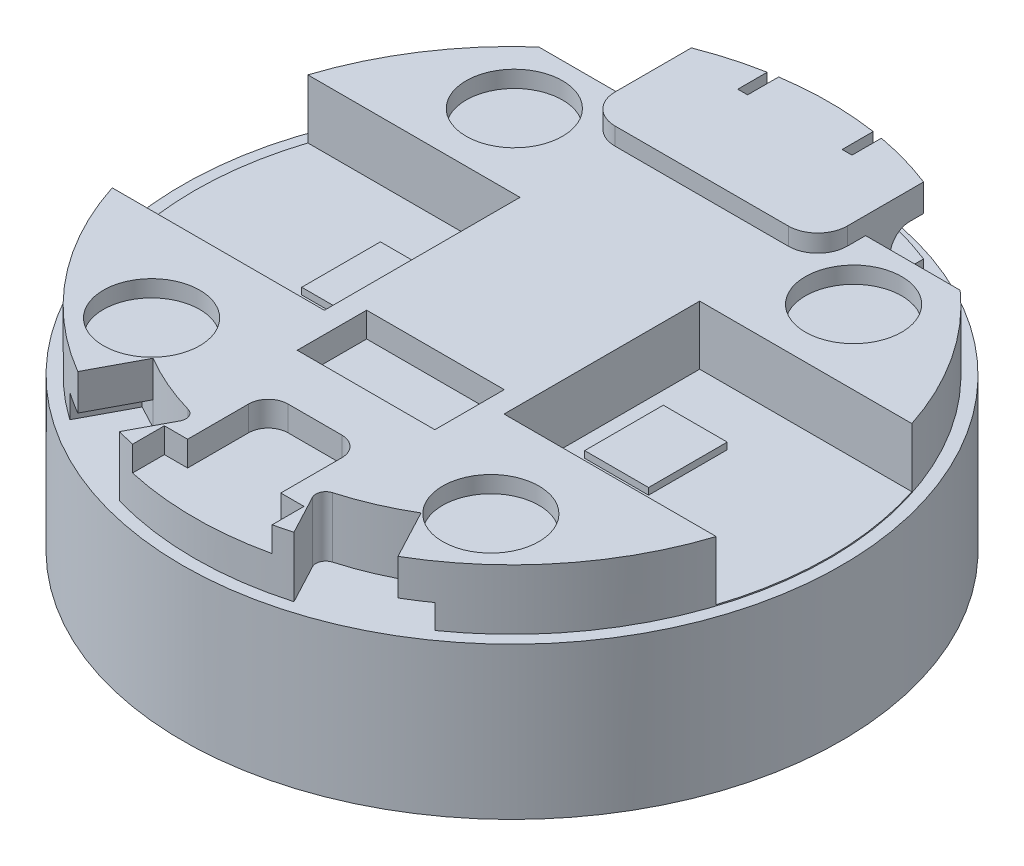
SolidWorks part; units mm, degrees
note: The reader was unsure of these and kept them because the rebuilt part matched: shared geometry of "Sketch26<4>", "Sketch26<7>".
ref_plane "Front Plane" through (0, 0, 0) normal (0, 0, 1) x (1, 0, 0)
ref_plane "Top Plane" through (0, 0, 0) normal (0, 1, 0) x (1, 0, 0)
ref_plane "Right Plane" through (0, 0, 0) normal (1, 0, 0) x (0, 0, -1)
sketch "Sketch1" plane through (0, 0, 0) normal (0, 1, 0) x (1, 0, 0)
  circle A0 centre (0, 0) radius 33.52
  dimension "D1" = 67.04
extrude "Boss-Extrude1" add sketch "Sketch1" along normal blind 9
sketch "Sketch2" plane through (0, 9, 0) normal (0, 1, 0) x (1, 0, 0)
  circle A0 centre (0, 0) radius 32.29
  dimension "D1" = 64.58
extrude "Boss-Extrude2" add sketch "Sketch2" along normal blind 6.12
sketch "Sketch3" plane through (0, 15.12, 0) normal (0, 1, 0) x (1, 0, 0)
  line L0 (0, 0) -> (0, 50000) construction
  line L1 (0, 0) -> (-50000, 0) construction
  line L2 (-11.81, 30.0528) -> (-11.81, 24.1537)
  line L3 (-11.81, 24.1537) -> (-21.43, 24.1537)
  line L4 (-11.81, 24.1537) -> (11.81, 24.1537) construction
  line L5 (11.81, 24.1537) -> (21.43, 24.1537)
  line L6 (11.81, 30.0528) -> (11.81, 24.1537)
  circle A0 centre (0, 0) radius 32.29 construction
  point P14 (0, 24.1537)
  circle M5 centre (0, 0) radius 32.29
  dimension "D1" = 9.62
  dimension "D2" = 11.81
extrude "Cut-Extrude1" cut sketch "Sketch3" against normal blind 6 contours L3 L2 M5 | L6 L5 M5
sketch "Sketch9" plane through (0, 15.12, 0) normal (0, 1, 0) x (1, 0, 0)
  line L0 (-11.81, 24.1537) -> (11.81, 24.1537) construction
  line L1 (-11.81, 28.6537) -> (11.81, 28.6537) construction
  line L2 (-11.81, 30.0528) -> (-11.81, 24.1537) construction
  line L3 (-11.81, 24.6537) -> (11.81, 24.6537) construction
  line L4 (11.81, 30.0528) -> (11.81, 24.1537) construction
  line L5 (0, 32.29) -> (-37.4588, 32.29) construction
  arc A1 (11.81, 30.0528) -> (-11.81, 30.0528) centre (0, 0) ccw construction
sketch "Sketch10" plane through (-11.81, 0, 0) normal (-1, 0, 0) x (0, 0, 1)
  line L0 (-28.6537, 15.12) -> (-28.6537, 9.12) construction
  line L1 (-30.0528, 9.12) -> (-24.1537, 9.12) construction
  line L2 (-24.6537, 15.12) -> (-24.6537, 9.12)
  line L3 (-33.7795, 12.12) -> (-23.5278, 12.12) construction
  line L4 (-28.6537, 9.12) -> (-35.6991, 9.12) construction
  line L5 (-28.6537, 10.12) -> (-37.7738, 10.12) construction
  circle A0 centre (-28.6537, 12.12) radius 2
  point P11 (-28.6537, 12.12)
  dimension "D1" = 4
extrude "Cut-Extrude2" cut sketch "Sketch10" against normal through all contours A0
ref_plane "Plane3" through (0, 0, 0) normal (-1, 0, 0) x (0, 0, 1)
sketch "Sketch19" plane through (0, 0, 0) normal (-1, 0, 0) x (0, 0, 1)
  line L0 (4.593, 17.1307) -> (4.593, -49982.8693) construction
  point P2 (-30.0416, 10.7027)
sketch "Sketch20" plane through (0, 0, 0) normal (-1, 0, 0) x (0, 0, 1)
  line L0 (-28.6537, 12.12) -> (-42.8447, 12.12) construction
sketch "Sketch23" plane through (-11.81, 0, 0) normal (-1, 0, 0) x (0, 0, 1)
  line L0 (-28.6537, 14.12) -> (-34.7082, 14.12)
  line L4 (-34.7082, 10.12) -> (-28.6537, 10.12)
  line L5 (-28.6537, 14.12) -> (-28.6537, 10.12)
  line L6 (-34.7082, 14.12) -> (-34.7082, 10.12)
  arc A0 (-30.0528, 10.6908) -> (-30.0528, 13.5492) centre (-28.6537, 12.12) ccw construction
extrude "Cut-Extrude3" cut sketch "Sketch23" against normal through all
sketch "Sketch24" plane through (0, 15.12, 0) normal (0, 1, 0) x (1, 0, 0)
  line L0 (0, 0) -> (-50000, 0) construction
  line L1 (0, 0) -> (0, 50000) construction
  line L2 (31.6, 6.6395) -> (19.5839, 6.6395)
  line L3 (19.5839, 6.6395) -> (19.5839, 0)
  line L4 (-2.2007, -32.2149) -> (-2.2007, -19.9749)
  line L5 (-2.2007, -19.9749) -> (0, -19.9749)
  line L6 (-11.81, 30.0528) -> (-11.81, 22.29)
  line L7 (-8.81, 19.29) -> (8.81, 19.29)
  line L8 (0, 32.29) -> (0, 19.29) construction
  line L9 (0, 32.29) -> (0, 19.29)
  line L10 (11.81, 30.0528) -> (11.81, 22.29)
  arc A0 (-21.43, 24.1537) -> (21.43, 24.1537) centre (0, 0) ccw construction
  arc A1 (11.81, 30.0528) -> (-11.81, 30.0528) centre (0, 0) ccw construction
  arc A2 (11.81, 22.29) -> (8.81, 19.29) centre (8.81, 22.29) cw
  arc A3 (-8.81, 19.29) -> (-11.81, 22.29) centre (-8.81, 22.29) cw
  point P26 (11.81, 19.29)
  point P29 (-11.81, 19.29)
  line M7 (-11.81, 30.0528) -> (-11.81, 24.1537)
  line M11 (11.81, 24.1537) -> (11.81, 30.0528)
  arc M12 (11.81, 30.0528) -> (-11.81, 30.0528) centre (0, 0) ccw
  dimension "D3" = 3
  dimension "D1" = 12.24
  dimension "D2" = 13
extrude "Boss-Extrude4" add sketch "Sketch24" along normal blind 1.78 contours A3 L7 L9 L6 M12 M7 | A2 L10 L9 L7 M11 M12
sketch "Sketch26" plane through (0, 15.12, 0) normal (0, 1, 0) x (1, 0, 0)
  line L0 (0, 0) -> (0, -50000) construction
  line L1 (0, 0) -> (-50000, 0) construction
  line L2 (30.7187, 9.95) -> (9.1387, 9.95)
  line L3 (9.1387, 9.95) -> (9.1387, -9.95)
  line L4 (30.7187, -9.95) -> (9.1387, -9.95)
  line L5 (-4.6587, 12.95) -> (4.6587, 12.95) construction
  line L6 (4.6587, 12.95) -> (4.6587, 0) construction
  line L7 (4.6587, 0) -> (4.6587, -14.85) construction
  line L8 (4.6587, -14.85) -> (0, -14.85) construction
  line L9 (-4.6587, -14.85) -> (0, -14.85) construction
  line L12 (0, 19.1985) -> (20.1, 19.1985) construction
  line L13 (20.1, 19.1985) -> (20.1, 9.95) construction
  line L14 (0, 32.1985) -> (-36.5688, 32.1985) construction
  line L15 (-7.1, -31.4997) -> (-7.1, -28.2597)
  line L16 (-7.1, -28.2597) -> (-4.74, -28.2597)
  line L17 (7.1, -31.4997) -> (7.1, -28.2597)
  line L19 (-4.74, -28.2597) -> (-4.74, -22.05)
  line L20 (-2.74, -20.05) -> (2.74, -20.05)
  line L21 (4.74, -28.2597) -> (4.74, -22.05)
  line L22 (0, -32.29) -> (21.7123, -32.29) construction
  line L23 (4.74, -28.2597) -> (7.1, -28.2597)
  line L26 (12.5921, 19.1985) -> (12.5921, 19.0001)
  line L27 (14.1577, 16.0217) -> (21.8513, 16.0217)
  line L40 (7, -14.85) -> (-7, -14.85)
  line L45 (-7, -14.85) -> (-7, -10.2285)
  line L46 (-7, -10.2285) -> (7, -10.2285)
  line L47 (7, -14.85) -> (7, -10.2285)
  line L48 (12.6302, 17.4892) -> (21.8766, 17.4892) construction
  line L50 (7.4988, -24.9826) -> (7.4988, -24.919)
  line L52 (8.0715, -24.9826) -> (8.0715, -24.919)
  line L53 (14.1577, 36.6941) -> (14.1577, 5.8809) construction
  arc A0 (-21.43, 24.1537) -> (21.43, 24.1537) centre (0, 0) ccw construction
  arc A2 (4.74, -22.05) -> (2.74, -20.05) centre (2.74, -22.05) ccw
  arc A3 (-2.74, -20.05) -> (-4.74, -22.05) centre (-2.74, -22.05) ccw
  circle A5 centre (17.2534, 17.4892) radius 4.9
  arc A6 (-14.4609, -22.3616) -> (-4.74, -26.2048) centre (0, 0) ccw
  circle A7 centre (17.2534, -19.4108) radius 4.9
  circle A8 centre (-17.2534, -19.4108) radius 4.9
  arc A9 (4.74, -26.2048) -> (15.2393, -21.8385) centre (0, 0) ccw
  circle A10 centre (-17.2534, 17.4892) radius 4.9
  point P10 (2.3294, -14.85)
  point P13 (9.1387, 0)
  point P22 (0, 12.95)
  point P31 (0, -28.2597)
  point P37 (0, -20.05)
  point P41 (4.74, -20.05)
  point P44 (-4.74, -20.05)
  point P63 (0, 0)
  point P66 (0, -10.2285)
  point P79 (14.1577, 21.2875)
  arc M17 (-21.43, 24.1537) -> (21.43, 24.1537) centre (0, 0) ccw
  dimension "D8" = 14.2
  dimension "D11" = 2
  dimension "D12" = 9.8
  dimension "D1" = 21.58
  dimension "D2" = 9.95
  dimension "D3" = 4.48
  dimension "D4" = 3
  dimension "D5" = 4.9
  dimension "D6" = 13
  dimension "D7" = 20.1
  dimension "D9" = 9.48
  dimension "D10" = 12.24
  dimension "D13" = 2
  dimension "D14" = 7
sketch "Sketch27" plane through (-11.81, 0, 0) normal (-1, 0, 0) x (0, 0, 1)
  line L0 (-28.4924, 16.9) -> (-35.5308, 16.9) construction
  line L1 (-30.0528, 16.9) -> (-22.29, 16.9) construction
extrude "Cut-Extrude5" cut sketch "Sketch26<4>" against normal blind 6 contours L4 L2 L3 M17
sketch "Sketch26<4>" plane through (0, 15.12, 0) normal (0, 1, 0) x (1, 0, 0) same geometry as "Sketch26"
extrude "Cut-Extrude6" cut sketch "Sketch26" against normal blind 2.54 contours L20 A3 L19 L16 L15 L17 L23 L21 A2 M17 | L40 L47 L46 L45
sketch "Sketch28" plane through (0, 15.12, 0) normal (0, 1, 0) x (1, 0, 0)
  line L0 (0, 0) -> (0, -50000) construction
  line L1 (-13.6253, -22.8803) -> (-16.283, -27.8839)
  line L2 (-6.1386, -25.9128) -> (-8.8666, -31.0488)
  line L3 (6.1386, -25.9128) -> (8.8666, -31.0488)
  line L4 (13.6253, -22.8803) -> (16.283, -27.8839)
  arc A0 (-13.6253, -22.8803) -> (-6.1386, -25.9128) centre (0, 0) ccw
  arc A1 (-21.43, 24.1537) -> (-7.1, -31.4997) centre (0, 0) ccw construction
  arc A2 (13.6253, -22.8803) -> (6.1386, -25.9128) centre (0, 0) cw
  arc M5 (7.1, -31.4997) -> (30.7187, -9.95) centre (0, 0) ccw
  arc M17 (-21.43, 24.1537) -> (-7.1, -31.4997) centre (0, 0) ccw
  dimension "D1" = 5.66
extrude "Cut-Extrude7" cut sketch "Sketch28" against normal up to surface (6.12 mm away) contours A0 L1 L2 M17 | L4 A2 L3 M5 up to face at (0, 9, 32.29)
sketch "Sketch30" plane through (-1.1486, 0, -0.6101) normal (0.8832, 0, 0.4691) x (0.4691, 0, -0.8832)
  line L0 (-32.2638, 12.66) -> (-26.5982, 12.66) construction
  line L1 (-32.2638, 11.46) -> (-26.5982, 11.46) construction
  line L3 (-32.2638, 12.66) -> (-26.5982, 12.66)
  line L4 (-32.2638, 9) -> (-26.5982, 9)
  line L5 (-26.5982, 9) -> (-26.5982, 15.12)
  line L6 (-26.5982, 15.12) -> (-32.2638, 15.12)
  line L7 (-32.2638, 15.12) -> (-32.2638, 9)
  line L8 (-32.2638, 9) -> (-26.5982, 9)
  line L9 (-26.5982, 9) -> (-26.5982, 15.12)
  line L10 (-26.5982, 15.12) -> (-32.2638, 15.12)
  line L11 (-32.2638, 15.12) -> (-32.2638, 9)
  line L12 (-32.2638, 12.66) -> (-32.2638, 11.46)
  line L13 (-32.2638, 11.46) -> (-26.5982, 11.46)
  line L14 (-26.5982, 12.66) -> (-26.5982, 11.46)
  line M7 (-32.2638, 9) -> (-26.5982, 9)
  line M8 (-26.5982, 9) -> (-26.5982, 15.12)
  dimension "D2" = 3.66
  dimension "D1" = 0
extrude "Cut-Extrude8" cut sketch "Sketch26<7>" against normal blind 1.7
sketch "Sketch26<7>" plane through (0, 15.12, 0) normal (0, 1, 0) x (1, 0, 0) same geometry as "Sketch26"
sketch "Sketch31" plane through (0, 16.9, 0) normal (0, 1, 0) x (1, 0, 0)
  line L0 (-5.81, 31.763) -> (-5.81, 28.77)
  line L1 (-4.81, 31.9297) -> (-4.81, 28.77)
  line L2 (-4.81, 28.77) -> (-5.81, 28.77)
  line L3 (-8.81, 19.29) -> (8.81, 19.29)
  line L4 (11.81, 22.29) -> (11.81, 30.0528)
  line L5 (-11.81, 30.0528) -> (-11.81, 22.29)
  line L6 (-8.81, 19.29) -> (8.81, 19.29)
  line L7 (11.81, 22.29) -> (11.81, 30.0528)
  line L8 (-11.81, 30.0528) -> (-11.81, 22.29)
  line L9 (0, 32.29) -> (-14.5468, 32.29) construction
  line L10 (0, 19.29) -> (0, 26.1672) construction
  line L11 (0, 4.2695) -> (0, -4.2695) construction
  line L12 (4.81, 28.77) -> (5.81, 28.77)
  line L13 (5.81, 31.763) -> (5.81, 28.77)
  line L14 (4.81, 31.9297) -> (4.81, 28.77)
  arc A3 (-11.81, 22.29) -> (-8.81, 19.29) centre (-8.81, 22.29) ccw
  arc A4 (8.81, 19.29) -> (11.81, 22.29) centre (8.81, 22.29) ccw
  arc A5 (11.81, 30.0528) -> (-11.81, 30.0528) centre (0, 0) ccw
  arc A6 (-11.81, 22.29) -> (-8.81, 19.29) centre (-8.81, 22.29) ccw
  arc A7 (8.81, 19.29) -> (11.81, 22.29) centre (8.81, 22.29) ccw
  arc A8 (11.81, 30.0528) -> (-11.81, 30.0528) centre (0, 0) ccw
  arc M16 (11.81, 30.0528) -> (-11.81, 30.0528) centre (0, 0) ccw
  dimension "D2" = 6
  dimension "D3" = 1
  dimension "D4" = 3.52
  dimension "D1" = 0
sketch "Sketch32" plane through (-1.1486, 0, -0.6101) normal (0.8832, 0, 0.4691) x (0.4691, 0, -0.8832)
sketch "Sketch33" plane through (-1.1486, 0, -0.6101) normal (0.8832, 0, 0.4691) x (0.4691, 0, -0.8832)
  line L0 (-32.2638, 11.46) -> (-26.5982, 11.46)
  line L2 (-32.2638, 12.66) -> (-32.2638, 11.46)
  line L4 (-26.5982, 12.66) -> (-26.5982, 11.46)
  line L8 (-32.2638, 9) -> (-26.5982, 9)
  line L9 (-26.5982, 9) -> (-26.5982, 15.12)
  line L10 (-26.5982, 15.12) -> (-32.2638, 15.12)
  line L11 (-32.2638, 15.12) -> (-32.2638, 9)
  line L12 (-32.2638, 9) -> (-26.5982, 9)
  line L13 (-26.5982, 9) -> (-26.5982, 15.12)
  line L14 (-26.5982, 15.12) -> (-32.2638, 15.12)
  line L15 (-32.2638, 15.12) -> (-32.2638, 9)
  dimension "D1" = 0
sketch "Sketch36" plane through (-1.1486, 0, -0.6101) normal (0.8832, 0, 0.4691) x (0.4691, 0, -0.8832)
  line L0 (-32.2638, 11.56) -> (-26.5982, 11.56)
  line L4 (-32.2638, 9) -> (-26.5982, 9)
  line L5 (-26.5982, 9) -> (-26.5982, 15.12)
  line L6 (-26.5982, 15.12) -> (-32.2638, 15.12)
  line L7 (-32.2638, 15.12) -> (-32.2638, 9)
  line L8 (-32.2638, 9) -> (-26.5982, 9)
  line L9 (-26.5982, 9) -> (-26.5982, 15.12)
  line L10 (-26.5982, 15.12) -> (-32.2638, 15.12)
  line L11 (-32.2638, 15.12) -> (-32.2638, 9)
  dimension "D2" = 2.56
  dimension "D1" = 0
sketch "Sketch37" plane through (1.1486, 0, -0.6101) normal (-0.8832, 0, 0.4691) x (0.4691, 0, 0.8832)
  line L0 (32.2638, 11.46) -> (26.5982, 11.46)
  line L4 (32.2638, 9) -> (32.2638, 15.12)
  line L5 (32.2638, 15.12) -> (26.5982, 15.12)
  line L6 (26.5982, 15.12) -> (26.5982, 9)
  line L7 (26.5982, 9) -> (32.2638, 9)
  line L8 (32.2638, 9) -> (32.2638, 15.12)
  line L9 (32.2638, 15.12) -> (26.5982, 15.12)
  line L10 (26.5982, 15.12) -> (26.5982, 9)
  line L11 (26.5982, 9) -> (32.2638, 9)
  line M6 (32.2638, 9) -> (32.2638, 15.12)
  line M8 (26.5982, 15.12) -> (26.5982, 9)
  line M9 (26.5982, 9) -> (32.2638, 9)
  dimension "D2" = 3.66
  dimension "D1" = 0
extrude "Cut-Extrude13" cut sketch "Sketch37" against normal blind 2.7 contours L0 M6 M8 M9
sketch "Sketch38" plane through (-1.1486, 0, -0.6101) normal (0.8832, 0, 0.4691) x (0.4691, 0, -0.8832)
  line L4 (-32.2638, 9) -> (-26.5982, 9)
  line L5 (-26.5982, 9) -> (-26.5982, 15.12)
  line L6 (-26.5982, 15.12) -> (-32.2638, 15.12)
  line L7 (-32.2638, 15.12) -> (-32.2638, 9)
  line L8 (-32.2638, 9) -> (-26.5982, 9)
  line L9 (-26.5982, 9) -> (-26.5982, 15.12)
  line L10 (-26.5982, 15.12) -> (-32.2638, 15.12)
  line L11 (-32.2638, 15.12) -> (-32.2638, 9)
  dimension "D1" = 0
extrude "Cut-Extrude14" cut sketch "Sketch30" against normal blind 2.7 contours L13 L11 M7 M8
sketch "Sketch40" plane through (0, 9.12, 0) normal (0, 1, 0) x (1, 0, 0)
  line L0 (9.1387, 9.95) -> (9.1387, -9.95) construction
  line L1 (11.1387, 4.25) -> (17.6387, 4.25)
  line L2 (11.1387, 4.25) -> (11.1387, -3.75)
  line L3 (11.1387, -3.75) -> (17.6387, -3.75)
  line L4 (17.6387, 4.25) -> (17.6387, -3.75)
  line L5 (30.7187, 9.95) -> (9.1387, 9.95) construction
  dimension "D1" = 8
  dimension "D2" = 6.5
  dimension "D3" = 2
  dimension "D4" = 5.7
extrude "Boss-Extrude5" add sketch "Sketch40" along normal blind 0.68
extrude "Cut-Extrude15" cut sketch "Sketch31" against normal blind 4.1 contours L2 L1 L0 M16 | L14 L12 L13 M16
sketch "Sketch41" plane through (0, 0, 0) normal (0, -1, 0) x (1, 0, 0)
  circle A0 centre (0, 0) radius 33.52
  circle A1 centre (0, 0) radius 33.52
  circle A2 centre (0, 0) radius 33.52
  circle M2 centre (0, 0) radius 33.52
  dimension "D1" = 0
extrude "Boss-Extrude6" add sketch "Sketch41" along normal blind 6.44 contours M2
sketch "Sketch43" plane through (0, 0, 10.2285) normal (0, 0, 1) x (1, 0, 0)
  line L4 (7, 15.12) -> (-7, 15.12)
  line L5 (-7, 15.12) -> (-7, 12.58)
  line L6 (-7, 12.58) -> (7, 12.58)
  line L7 (7, 12.58) -> (7, 15.12)
  line L8 (7, 15.12) -> (-7, 15.12)
  line L9 (-7, 15.12) -> (-7, 12.58)
  line L10 (-7, 12.58) -> (7, 12.58)
  line L11 (7, 12.58) -> (7, 15.12)
  dimension "D1" = 0
extrude "Cut-Extrude16" cut sketch "Sketch43" against normal blind 2.44
sketch "Sketch44" plane through (0, 15.12, 0) normal (0, 1, 0) x (1, 0, 0)
  line L0 (0, 0) -> (0, 50000) construction
ref_plane "Plane4" through (0, 0, 0) normal (-1, 0, 0) x (0, 0, 1)
mirror "Mirror1" about plane through (0, 0, 0) normal (-1, 0, 0) of "Cut-Extrude5"
mirror "Mirror2" about plane through (0, 0, 0) normal (-1, 0, 0) of "Boss-Extrude5"
fillet "Fillet1" radius 1 1 edges at (6.1386, 12.06, 25.9128)
fillet "Fillet2" radius 1 1 edges at (-6.1386, 12.06, 25.9128)
